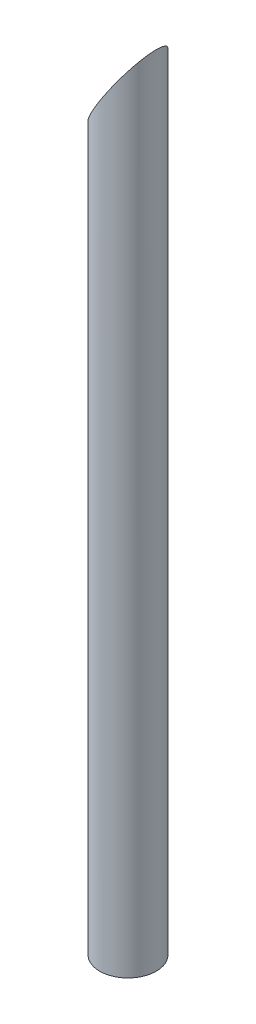
SolidWorks part; units mm, degrees
material "Alloy Steel"
ref_plane "Front Plane" through (0, 0, 0) normal (0, 0, 1) x (1, 0, 0)
ref_plane "Top Plane" through (0, 0, 0) normal (0, 1, 0) x (1, 0, 0)
ref_plane "Right Plane" through (0, 0, 0) normal (1, 0, 0) x (0, 0, -1)
other "Configuration Table"
sketch "Sketch1" plane through (0, 0, 0) normal (0, 1, 0) x (1, 0, 0)
  circle A0 centre (0, 0) radius 3.5052
  dimension "D1" = 7.0104
extrude "Boss-Extrude1" add sketch "Sketch1" along normal blind 99.0092
sketch "Sketch2" plane through (0, 0, 0) normal (0, 0, 1) x (1, 0, 0)
  line L0 (-3.5052, 88.011) -> (3.5052, 99.0092)
  line L1 (-3.5052, 99.0092) -> (-3.5052, 0) construction
  line L2 (-3.5052, 88.011) -> (-3.5052, 99.0092)
  line L3 (-3.5052, 99.0092) -> (3.5052, 99.0092)
  dimension "D1" = 10.9982
extrude "Cut-Extrude1" cut sketch "Sketch2" against normal mid plane 99.0092
sketch "Sketch3" plane through (0, 0, 0) normal (0, -1, 0) x (1, 0, 0)
  circle A0 centre (0, 0) radius 3.175
  dimension "D1" = 6.35
extrude "Cut-Extrude2" cut sketch "Sketch3" against normal blind 76.2
sketch "Sketch4" plane through (0, 76.2, 0) normal (0, -1, 0) x (1, 0, 0)
  circle A0 centre (0, 0) radius 2.5019
  dimension "D1" = 5.0038
extrude "Cut-Extrude3" cut sketch "Sketch4" against normal blind 76.2
ref_plane "Plane1" through (0, 81.28, 0) normal (0, 1, 0) x (1, 0, 0)
sketch "Sketch6" plane through (0, 81.28, 0) normal (0, 1, 0) x (1, 0, 0)
  circle A0 centre (0, 0) radius 3.429
  dimension "D1" = 6.858
extrude "Cut-Extrude4" cut sketch "Sketch6" along normal blind 76.2
ref_plane "Plane2" through (0, 21.0058, 0) normal (0, 1, 0) x (1, 0, 0)
thread "Thread1" pitch 0.3175 method extrude profile "Thread Profile1" start angle 0, offset 0, length 5.5372, pitch 0.7937, diameter 6.35
ref_plane "Plane3" through (3.175, 0, 0) normal (0, 0, 1) x (1, 0, 0)
sketch "Thread Profile1" plane through (3.175, 0, 0) normal (0, 0, 1) x (1, 0, 0)
  line L0 (0, 0) -> (0, 0.3175) construction
  line L11 (0, 0) -> (0, 0.2778)
  line L12 (0, 0.2778) -> (-0.1719, 0.1786)
  line L13 (-0.1719, 0.1786) -> (-0.1719, 0.0992)
  line L15 (-0.1719, 0.0992) -> (0, 0)
  line L17 (-0.1719, 0.1389) -> (0, 0.1389) construction
  point P2 (0, 0)
  dimension "Pitch" = 0.3175
  dimension "Profile_Angle" = 60
  dimension "Profile_Land" = 0.0794
  dimension "Profile_Height" = 0.1719
